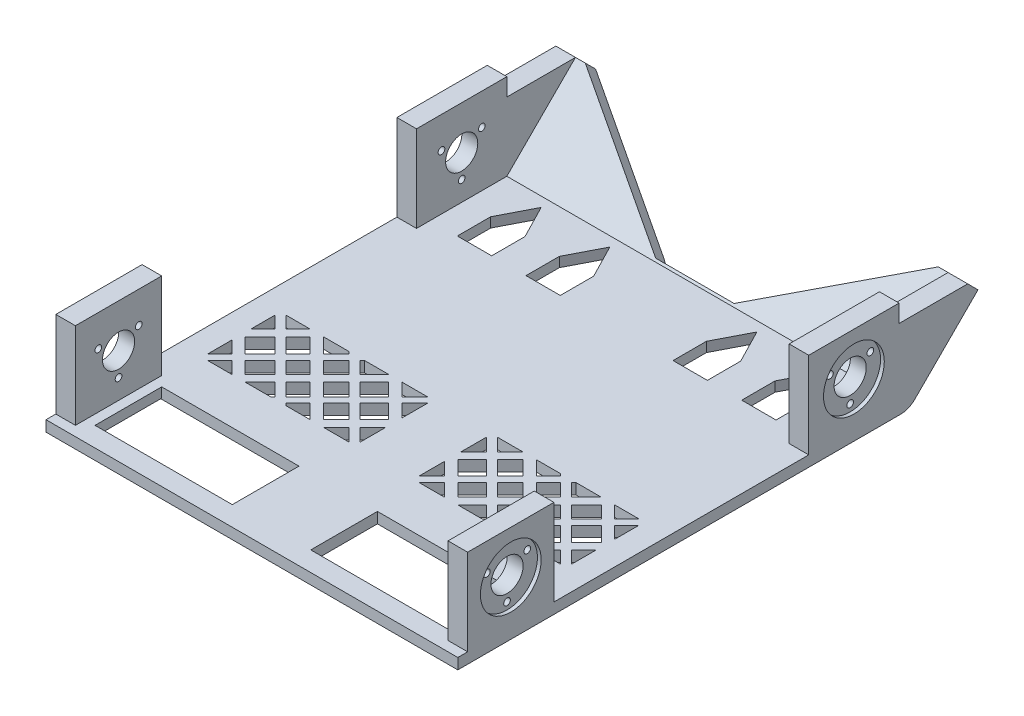
SolidWorks part; units mm, degrees
ref_plane "前视基准面" through (0, 0, 0) normal (0, 0, 1) x (1, 0, 0)
ref_plane "上视基准面" through (0, 0, 0) normal (0, 1, 0) x (1, 0, 0)
ref_plane "右视基准面" through (0, 0, 0) normal (1, 0, 0) x (0, 0, -1)
sketch "草图1" plane through (0, 0, 0) normal (0, 1, 0) x (1, 0, 0)
  line L0 (0, 0) -> (210, 0)
  line L1 (210, 0) -> (210, -230)
  line L2 (210, -230) -> (0, -230)
  line L3 (0, -230) -> (0, 0)
  line L4 (0, 0) -> (3, 0)
  line L5 (0, 0) -> (5, 0)
  line L6 (5, 0) -> (5, -230)
  line L7 (210, 0) -> (205, 0)
  line L8 (205, 0) -> (205, -230)
  line L9 (0, 0) -> (0, -10)
  line L10 (0, -10) -> (210, -10)
  line L11 (210, -230) -> (210, -220)
  line L12 (210, -220) -> (0, -220)
  line L13 (5, -10) -> (85, -10)
  line L14 (85, -10) -> (85, -44)
  line L15 (85, -44) -> (5, -44)
  line L16 (205, -10) -> (125, -10)
  line L17 (125, -10) -> (125, -44)
  line L18 (125, -44) -> (205, -44)
  line L19 (5, -220) -> (5, -186)
  line L20 (5, -186) -> (85, -186)
  line L21 (85, -186) -> (85, -220)
  line L22 (85, -220) -> (5, -220)
  line L23 (205, -220) -> (125, -220)
  line L24 (125, -220) -> (125, -186)
  line L25 (125, -186) -> (205, -186)
  line L26 (205, -186) -> (205, -220)
  line L27 (5, -10) -> (5, -44)
  line L28 (205, -44) -> (205, -10)
extrude "凸台-拉伸1" add sketch "草图1" along normal blind 5.5 contours L24 L25 L8 L18 L17 L10 L14 L15 L6 L20 L21 L12 | L3 L10 L6 L0 | L12 L6 L10 L3 | L6 L10 L8 L0 | L12 L1 L10 L8 | L8 L10 L1 L0 | L8 L12 L6 L2 | L6 L12 L3 L2 | L1 L12 L8 L2 region at (2.5, 0, 5) region at (2.5, 0, 115) region at (105, 0, 5) region at (2.5, 0, 225) region at (207.5, 0, 5) region at (105, 0, 225) region at (105, 0, 115) region at (207.5, 0, 115) region at (207.5, 0, 225)
sketch "草图3" plane through (0, 5.5, 0) normal (0, 1, 0) x (1, 0, 0)
  line L0 (85, -10) -> (85, 0)
  line L1 (0, 0) -> (210, 0) construction
  line L2 (85, 0) -> (85, -5)
  line L3 (85, -5) -> (0, -5)
  line L4 (0, -230) -> (0, 0) construction
  line L5 (0, -5) -> (0, -46.0662)
  line L6 (0, -46.0662) -> (0, -51.0662)
  line L7 (0, -51.0662) -> (5, -51.0662)
  line L8 (5, -51.0662) -> (5, -5)
  line L9 (105, 0) -> (105, -230)
  line L10 (210, -230) -> (0, -230) construction
  line L11 (5, -220) -> (5, -225)
  line L12 (5, -225) -> (0, -225)
  line L13 (0, -225) -> (0, -181)
  line L14 (0, -181) -> (5, -181)
  line L15 (5, -181) -> (5, -220)
  line L16 (210, -181) -> (205, -181)
  line L17 (210, -225) -> (210, -181)
  line L18 (205, -225) -> (210, -225)
  line L19 (205, -220) -> (205, -225)
  line L20 (205, -181) -> (205, -220)
  line L21 (5, -5) -> (5, -51.0662)
  line L22 (0, -51.0662) -> (0, -5)
  line L23 (210, -46.0662) -> (210, -51.0662)
  line L24 (210, -51.0662) -> (205, -51.0662)
  line L25 (205, -51.0662) -> (205, -5)
  line L26 (210, -5) -> (210, -46.0662)
  line L27 (205, -5) -> (210, -5)
extrude "凸台-拉伸2" add sketch "草图3" along normal blind 44 contours L7 L8 L17 L3 L10 | L15 L14 L10 L12 L11 L26 | L16 L20 L6 L19 L18 L2 | L27 L25 L22 L24 L2 region at (2.5, 5.5, 28.0331) region at (2.5, 5.5, 203) region at (207.5, 5.5, 203) region at (207.5, 5.5, 28.0331)
sketch "草图4" plane through (0, 0, 0) normal (-1, 0, 0) x (0, 0, 1)
  line L0 (5, 49.5) -> (51.0662, 5.5)
  line L1 (181, 49.5) -> (225, 5.5)
  circle A1 centre (203, 27.5) radius 17
  circle A2 centre (28.0331, 27.5) radius 15
  circle A3 centre (28.0331, 27.5) radius 8.2
  circle A4 centre (28.0331, 27.5) radius 11.9
  circle A5 centre (28.0331, 15.6) radius 1.7
  circle A6 centre (17.7274, 33.45) radius 1.7
  circle A7 centre (38.3388, 33.45) radius 1.7
  point P24 (28.0331, 27.5)
  dimension "D1" = 3
extrude "切除-拉伸1" cut sketch "草图4" against normal through all both and the other way through all contours A4 A6 | A4 A6 | A4 A7 | A4 A7 | A4 A5 | A4 A5 | L0 A3 | L0 A3 region at (0, 30.0167, 30.4369) region at (0, 24.9833, 25.6293) region at (0, 33.7996, 38.9443) region at (0, 33.0785, 37.6954) region at (0, 33.0785, 18.3708) region at (0, 33.7996, 17.1219) region at (0, 14.9008, 28.0331) region at (0, 16.3429, 28.0331)
sketch "草图5" plane through (0, 0, 0) normal (-1, 0, 0) x (0, 0, 1)
  circle A1 centre (28.0331, 27.5) radius 15.5
extrude "切除-拉伸3" cut sketch "草图5" against normal blind 1.9
sketch "草图6" plane through (210, 0, 0) normal (1, 0, 0) x (0, 0, -1)
  circle A0 centre (-28.0331, 27.5) radius 15.5
extrude "切除-拉伸4" cut sketch "草图6" against normal blind 1.9
sketch "草图7" plane through (0, 0, 0) normal (-1, 0, 0) x (0, 0, 1)
  line L0 (181, 49.5) -> (225, 5.5)
  line L1 (203, 27.5) -> (203, 15.6)
  circle A0 centre (203, 27.5) radius 11.9
  circle A1 centre (203, 27.5) radius 8.2
  circle A2 centre (203, 15.6) radius 1.7
  circle A3 centre (192.6943, 33.45) radius 1.7
  circle A4 centre (213.3057, 33.45) radius 1.7
  point P15 (203, 27.5)
  dimension "D1" = 3
extrude "切除-拉伸5" cut sketch "草图7" against normal through all both and the other way through all contours A0 A3 | A0 A3 | A0 A4 | A0 A4 | A0 A2 L1 | L1 A2 A0 | A0 A2 | L0 A1 | L0 A1 L1 | L1 A1 L0 region at (0, 29.9609, 205.4609) region at (0, 25.8594, 199.0393) region at (0, 33.7996, 213.9112) region at (0, 33.0785, 212.6623) region at (0, 33.0785, 193.3377) region at (0, 33.7996, 192.0888) region at (0, 22.5783, 205.0386) region at (0, 16.3429, 203.7042) region at (0, 16.3429, 202.2958) region at (0, 14.9008, 203)
sketch "草图8" plane through (0, 0, 0) normal (-1, 0, 0) x (0, 0, 1)
  circle A0 centre (203, 27.5) radius 15.5
extrude "切除-拉伸6" cut sketch "草图8" against normal blind 1.9
sketch "草图9" plane through (210, 0, 0) normal (1, 0, 0) x (0, 0, -1)
  circle A0 centre (-203, 27.5) radius 15.5
extrude "切除-拉伸7" cut sketch "草图9" against normal blind 1.9
sketch "草图10" plane through (0, 5.5, 0) normal (0, 1, 0) x (1, 0, 0)
  line L0 (5, -10) -> (15, -10)
  line L1 (5, -10) -> (85, -10) construction
  line L2 (15, -10) -> (15, -220)
  line L3 (85, -220) -> (5, -220) construction
  line L4 (15, -220) -> (5, -220)
  line L5 (5, -220) -> (5, -186)
  line L6 (5, -181) -> (5, -225) construction
  line L7 (5, -181) -> (5, -186) construction
  line L8 (5, -186) -> (15, -186)
  line L9 (5, -186) -> (85, -186) construction
  line L10 (5, -10) -> (5, -44)
  line L11 (5, -44) -> (15, -44)
  line L12 (85, -44) -> (5, -44) construction
  line L13 (205, -10) -> (195, -10)
  line L14 (125, -10) -> (205, -10) construction
  line L15 (195, -10) -> (195, -220)
  line L16 (205, -220) -> (125, -220) construction
  line L17 (195, -220) -> (205, -220)
  line L18 (205, -220) -> (205, -186)
  line L19 (205, -186) -> (195, -186)
  line L20 (125, -186) -> (205, -186) construction
  line L21 (205, -10) -> (205, -44)
  line L22 (205, -44) -> (195, -44)
  line L23 (125, -44) -> (205, -44) construction
  line M7 (5, -10) -> (85, -10)
  line M9 (85, -44) -> (5, -44)
  line M15 (5, -186) -> (85, -186)
  line M17 (85, -220) -> (5, -220)
  line M25 (205, -220) -> (125, -220)
  line M27 (125, -186) -> (205, -186)
  line M33 (205, -44) -> (125, -44)
  line M35 (125, -10) -> (205, -10)
extrude "凸台-拉伸3" add sketch "草图10" against normal blind 5 contours L21 L15 M35 M33 | L10 L2 M7 M9 | L5 L2 M17 M15 | L18 L15 M25 M27 region at (10, 5.5, 203) region at (10, 5.5, 27) region at (200, 5.5, 27) region at (200, 5.5, 203)
sketch "草图11" plane through (0, 5.5, 0) normal (0, 1, 0) x (1, 0, 0)
  line L0 (15, -10) -> (5, -10)
  line L1 (5, -51.0662) -> (5, -5) construction
  line L2 (10, -10) -> (10, -51.0662)
  line L3 (10, -51.0662) -> (5, -51.0662)
  line L4 (5, -51.0662) -> (5, -5)
  line L5 (5, -5) -> (10, -5)
  line L6 (10, -5) -> (10, -10)
  line L7 (10, -51.0662) -> (10, -230)
  line L8 (210, -230) -> (0, -230) construction
  line L9 (5, -225) -> (10, -225)
  line L10 (5, -181) -> (10, -181)
  line L11 (10, -181) -> (10, -225)
  line L12 (5, -181) -> (5, -225)
  line L13 (195, -10) -> (205, -10)
  line L14 (205, -51.0662) -> (205, -5) construction
  line L15 (200, -10) -> (200, -51.0662)
  line L16 (200, -51.0662) -> (205, -51.0662)
  line L17 (205, -51.0662) -> (205, -5)
  line L18 (205, -5) -> (200, -5)
  line L19 (200, -5) -> (200, -10)
  line L20 (200, -225) -> (205, -225)
  line L21 (205, -225) -> (205, -181)
  line L22 (205, -181) -> (200, -181)
  line L23 (200, -181) -> (200, -225)
  line M6 (5, -181) -> (5, -225)
  line M12 (205, -225) -> (205, -181)
  line M16 (205, -51.0662) -> (205, -5)
  line M22 (5, -5) -> (5, -51.0662)
extrude "凸台-拉伸4" add sketch "草图11" along normal blind 44 contours L3 L2 L0 M22 | L6 L5 L0 M22 | L18 L19 L13 M16 | L15 L16 L13 M16 | L10 L9 L7 M6 | L22 L23 L20 M12 region at (7.5, 5.5, 30.5331) region at (7.5, 5.5, 203) region at (7.5, 5.5, 7.5) region at (202.5, 5.5, 7.5) region at (202.5, 5.5, 30.5331) region at (202.5, 5.5, 203)
sketch "草图12" plane through (1.9, 0, 0) normal (-1, 0, 0) x (0, 0, 1)
  circle A0 centre (17.7274, 33.45) radius 1.7
  circle A1 centre (38.3388, 33.45) radius 1.7
  circle A2 centre (28.0331, 15.6) radius 1.7
  circle A3 centre (28.0331, 27.5) radius 8.2
  circle A4 centre (192.6943, 33.45) radius 1.7
  circle A5 centre (213.3057, 33.45) radius 1.7
  circle A6 centre (203, 15.6) radius 1.7
  circle A7 centre (203, 27.5) radius 8.2
extrude "切除-拉伸8" cut sketch "草图12" against normal through all both and the other way through all
sketch "草图13" plane through (210, 0, 0) normal (1, 0, 0) x (0, 0, -1)
  line L0 (-5, 5.5) -> (14.6466, 25.1466)
sketch "草图15" plane through (210, 0, 0) normal (1, 0, 0) x (0, 0, -1)
  line L0 (-5, 5.5) -> (-5, 40.5)
  line L1 (-5, 49.5) -> (-5, 5.5) construction
  line L2 (-5, 40.5) -> (31.0178, 40.5)
ref_plane "基准面5" through (0, 5.25, 5.25) normal (0, 0.7071, 0.7071) x (1, 0, 0)
sketch "草图17" plane through (0, 5.25, 5.25) normal (0, 0.7071, 0.7071) x (1, 0, 0)
  line L0 (210, 0.3536) -> (210, 49.8474)
  line L1 (210, 49.8474) -> (0, 49.8474)
  line L2 (0, 49.8474) -> (0, 0.3536)
  line L3 (0, 0.3536) -> (210, 0.3536)
extrude "凸台-拉伸5" add sketch "草图17" against normal through all
sketch "草图18" plane through (0, 0, 0) normal (-1, 0, 0) x (0, 0, 1)
  line L0 (-29.9975, 40.4975) -> (5, 40.5)
  line L1 (5, 40.5) -> (5, 5.5)
  line L2 (5, 5.5) -> (-29.9975, 40.4975)
extrude "凸台-拉伸6" add sketch "草图18" against normal blind 10
sketch "草图19" plane through (210, 0, 0) normal (1, 0, 0) x (0, 0, -1)
  line L0 (30, 40.5) -> (-5, 40.5)
  line L1 (-5, 40.5) -> (31.0178, 40.5) construction
  line L2 (40.3406, 50.8406) -> (-50.8406, -40.3406) construction
  line L3 (-5, 40.5) -> (-5, 5.5)
  line L4 (-5, 5.5) -> (30, 40.5)
extrude "凸台-拉伸8" add sketch "草图19" against normal blind 10
sketch "草图20" plane through (0, 5.25, 5.25) normal (0, 0.7071, 0.7071) x (1, 0, 0)
  line L0 (15, -3.182) -> (15, 49.8474)
  line L1 (200, 49.8474) -> (10, 49.8474) construction
  line L4 (125, 49.8474) -> (85, 49.8474)
  line L5 (85, 1.6082) -> (125, 1.6082)
  line L6 (125, 1.6082) -> (125, 49.8474)
  line L7 (85, 49.8474) -> (125, 49.8474)
  line L8 (85, 1.6082) -> (85, 49.8474)
  line L9 (15, 49.8474) -> (85, 1.6082)
  line L10 (195, -3.182) -> (195, 49.8474)
  line L11 (195, 49.8474) -> (125, 1.6082)
  line L12 (15, 1.6082) -> (85, 1.6082)
  line L13 (125, 1.6082) -> (195, 1.6082)
  line L14 (195, 1.6082) -> (195, 49.8474)
  line M4 (200, 49.8474) -> (10, 49.8474)
extrude "切除-拉伸9" cut sketch "草图20" against normal blind 10 contours L9 L8 M4 | L8 L5 L6 M4 | L11 L6 M4 region at (61.6667, 29.1274, -18.6274) region at (105, 23.4423, -12.9423) region at (148.3333, 29.1274, -18.6274)
sketch "草图21" plane through (0, 5.5, 0) normal (0, 1, 0) x (1, 0, 0)
  line L1 (15, -10) -> (85, -10) construction
  line L4 (125, -10) -> (195, -10) construction
  line L6 (32.5, -10) -> (15, -44)
  line L7 (32.5, -10) -> (50, -44)
  line L8 (85, -44) -> (15, -44) construction
  line L9 (50, -44) -> (67.5, -10)
  line L10 (67.5, -10) -> (85, -44)
  line L11 (125, -44) -> (142.5, -10)
  line L12 (142.5, -10) -> (160, -44)
  line L14 (160, -44) -> (177.5, -10)
  line L15 (177.5, -10) -> (195, -44)
  line L16 (15, -44) -> (15, -10)
  line L17 (15, -10) -> (32.5, -10)
  line L18 (32.5, -10) -> (67.5, -10)
  line L19 (67.5, -10) -> (85, -10)
  line L20 (85, -10) -> (85, -44)
  line L21 (125, -44) -> (125, -10)
  line L22 (125, -10) -> (142.5, -10)
  line L23 (142.5, -10) -> (177.5, -10)
  line L24 (177.5, -10) -> (195, -10)
  line L25 (195, -10) -> (195, -44)
  line L26 (41.25, -27) -> (41.25, -44)
  line L27 (58.75, -27) -> (58.75, -44)
  line L28 (151.25, -27) -> (151.25, -44)
  line L29 (125, -44) -> (195, -44) construction
  line L30 (168.75, -27) -> (168.75, -44)
  line L31 (41.25, -44) -> (58.75, -44)
  line L32 (151.25, -44) -> (168.75, -44)
  line M21 (15, -44) -> (15, -10)
  line M22 (15, -10) -> (85, -10)
  line M23 (85, -10) -> (85, -44)
  line M24 (85, -44) -> (15, -44)
  line M29 (125, -10) -> (195, -10)
  line M30 (195, -10) -> (195, -44)
  line M31 (195, -44) -> (125, -44)
  line M32 (125, -44) -> (125, -10)
extrude "凸台-拉伸11" add sketch "草图21" against normal blind 5 contours L6 M22 M21 | L7 L9 M22 | L7 L26 M24 | L27 L9 M24 | L10 M22 M23 | L11 M32 M29 | L12 L14 M29 | L15 M29 M30 | L30 L14 M31 | L12 L28 M31 region at (50, 5.5, 21.3333) region at (20.8333, 5.5, 21.3333) region at (44.1667, 5.5, 38.3333) region at (79.1667, 5.5, 21.3333) region at (55.8333, 5.5, 38.3333) region at (130.8333, 5.5, 21.3333) region at (160, 5.5, 21.3333) region at (154.1667, 5.5, 38.3333) region at (189.1667, 5.5, 21.3333) region at (165.8333, 5.5, 38.3333)
sketch "草图22" plane through (0, 0, 0) normal (-1, 0, 0) x (0, 0, 1)
  line L0 (0, 0.5) -> (0, 0)
  line L1 (0, 0) -> (-0.25, 0.25)
  line L2 (-0.25, 0.25) -> (0, 0.5)
extrude "凸台-拉伸13" add sketch "草图22" against normal blind 210
fillet "圆角1" radius 10 1 edges at (105, 0, 0)
sketch "草图23" plane through (0, 5.5, 0) normal (0, 1, 0) x (1, 0, 0)
  line L0 (23.75, -27) -> (23.75, -44)
  line L1 (32.5, -10) -> (15, -44) construction
  line L2 (41.25, -44) -> (15, -44) construction
  line L3 (23.75, -44) -> (15, -44)
  line L4 (15, -44) -> (23.75, -27)
  line L5 (76.25, -27) -> (76.25, -44)
  line L6 (67.5, -10) -> (85, -44) construction
  line L7 (85, -44) -> (58.75, -44) construction
  line L8 (76.25, -44) -> (85, -44)
  line L9 (85, -44) -> (76.25, -27)
  line L10 (133.75, -27) -> (133.75, -44)
  line L11 (125, -44) -> (142.5, -10) construction
  line L12 (125, -44) -> (151.25, -44) construction
  line L13 (133.75, -44) -> (125, -44)
  line L14 (125, -44) -> (133.75, -27)
  line L15 (186.25, -27) -> (186.25, -44)
  line L16 (177.5, -10) -> (195, -44) construction
  line L17 (168.75, -44) -> (195, -44) construction
  line L18 (186.25, -44) -> (195, -44)
  line L19 (195, -44) -> (186.25, -27)
extrude "凸台-拉伸14" add sketch "草图23" against normal blind 5 contours L4 L0 L3 | L9 L5 L8 | L14 L10 L13 | L19 L15 L18
sketch "草图24" plane through (0, 5.5, 0) normal (0, 1, 0) x (1, 0, 0)
  line L0 (0, -116.0331) -> (210, -116.0331) construction
  line L1 (0, -181) -> (0, -51.0662) construction
  line L2 (210, -51.0662) -> (210, -181) construction
  line L3 (105, -230) -> (105, -5) construction
  line L4 (210, -230) -> (0, -230) construction
  line L5 (10, -5) -> (200, -5) construction
  line L6 (197.8, -162.6296) -> (120, -162.6296)
  line L7 (12.2, -122.6296) -> (90, -122.6296)
  line L8 (12.2, -122.6296) -> (12.2, -162.6296)
  line L9 (12.2, -162.6296) -> (90, -162.6296)
  line L10 (90, -122.6296) -> (90, -162.6296)
  line L11 (120, -122.6296) -> (120, -162.6296)
  line L12 (197.8, -122.6296) -> (120, -122.6296)
  line L13 (197.8, -122.6296) -> (197.8, -162.6296)
  line L14 (12.2, -125.4296) -> (18.3835, -131.6131)
  line L15 (15, -122.6296) -> (21.1835, -128.8131)
  line L16 (90, -125.4296) -> (83.5137, -131.9159)
  line L17 (87.2, -122.6296) -> (80.7137, -129.1159)
  line L18 (12.2, -159.8296) -> (18.3835, -153.6461)
  line L19 (47.2, -122.6296) -> (48.3, -123.7296)
  line L20 (90, -159.8296) -> (83.5137, -153.3433)
  line L21 (15, -162.6296) -> (21.1835, -156.4461)
  line L22 (30.7972, -126.0598) -> (38.3835, -133.6461)
  line L23 (34.2274, -122.6296) -> (41.8137, -130.2159)
  line L24 (70.7972, -126.0598) -> (63.5137, -133.3433)
  line L25 (67.367, -122.6296) -> (60.0835, -129.9131)
  line L26 (74.2274, -162.6296) -> (80.7137, -156.1433)
  line L27 (70.7972, -159.1994) -> (77.2835, -152.7131)
  line L28 (27.367, -162.6296) -> (21.1835, -156.4461)
  line L29 (30.7972, -159.1994) -> (24.6137, -153.0159)
  line L30 (27.367, -122.6296) -> (21.1835, -128.8131)
  line L31 (30.7972, -126.0598) -> (24.6137, -132.2433)
  line L32 (74.2274, -122.6296) -> (80.7137, -129.1159)
  line L33 (70.7972, -126.0598) -> (77.2835, -132.5461)
  line L34 (18.3835, -131.6131) -> (12.2, -137.7966)
  line L35 (24.6137, -132.2433) -> (32.2, -139.8296)
  line L36 (21.8137, -135.0433) -> (29.4, -142.6296)
  line L37 (21.8137, -135.0433) -> (14.2274, -142.6296)
  line L38 (44.6137, -133.0159) -> (50.7972, -139.1994)
  line L39 (41.8137, -130.2159) -> (48.3, -123.7296)
  line L40 (41.1835, -136.4461) -> (47.367, -142.6296)
  line L41 (44.6137, -133.0159) -> (51.1, -126.5296)
  line L42 (32.2, -139.8296) -> (38.3835, -133.6461)
  line L43 (32.2, -145.4296) -> (38.3835, -151.6131)
  line L44 (35, -142.6296) -> (41.1835, -148.8131)
  line L45 (35, -142.6296) -> (41.1835, -136.4461)
  line L46 (21.8137, -150.2159) -> (29.4, -142.6296)
  line L47 (18.3835, -153.6461) -> (12.2, -147.4626)
  line L48 (21.8137, -150.2159) -> (14.2274, -142.6296)
  line L49 (24.6137, -153.0159) -> (32.2, -145.4296)
  line L50 (41.8137, -155.0433) -> (48.3, -161.5296)
  line L51 (44.6137, -152.2433) -> (51.1, -158.7296)
  line L52 (50.7972, -146.0598) -> (57.2835, -152.5461)
  line L53 (54.2274, -142.6296) -> (60.7137, -149.1159)
  line L54 (60.7137, -136.1433) -> (67.2, -142.6296)
  line L55 (60.0835, -129.9131) -> (53.9, -123.7296)
  line L56 (77.2835, -132.5461) -> (70, -139.8296)
  line L57 (80.0835, -135.3461) -> (72.8, -142.6296)
  line L58 (80.0835, -149.9131) -> (72.8, -142.6296)
  line L59 (80.7137, -156.1433) -> (87.2, -162.6296)
  line L60 (60.0835, -155.3461) -> (53.9, -161.5296)
  line L61 (57.2835, -152.5461) -> (51.1, -158.7296)
  line L62 (50.7972, -146.0598) -> (44.6137, -152.2433)
  line L63 (47.367, -142.6296) -> (41.1835, -148.8131)
  line L64 (51.1, -126.5296) -> (57.2835, -132.7131)
  line L65 (53.9, -123.7296) -> (55, -122.6296)
  line L66 (57.2835, -132.7131) -> (50.7972, -139.1994)
  line L67 (60.7137, -136.1433) -> (54.2274, -142.6296)
  line L68 (67.2, -142.6296) -> (60.7137, -149.1159)
  line L69 (70, -145.4296) -> (63.5137, -151.9159)
  line L70 (80.0835, -149.9131) -> (87.367, -142.6296)
  line L71 (83.5137, -153.3433) -> (90, -146.857)
  line L72 (38.3835, -151.6131) -> (30.7972, -159.1994)
  line L73 (41.8137, -155.0433) -> (34.2274, -162.6296)
  line L74 (48.3, -161.5296) -> (47.2, -162.6296)
  line L75 (53.9, -161.5296) -> (55, -162.6296)
  line L76 (60.0835, -155.3461) -> (67.367, -162.6296)
  line L77 (63.5137, -151.9159) -> (70.7972, -159.1994)
  line L78 (70, -145.4296) -> (77.2835, -152.7131)
  line L79 (70, -139.8296) -> (63.5137, -133.3433)
  line L80 (80.0835, -135.3461) -> (87.367, -142.6296)
  line L81 (83.5137, -131.9159) -> (90, -138.4021)
  line L82 (126.4863, -131.9159) -> (120, -138.4021)
  line L83 (129.9165, -135.3461) -> (122.633, -142.6296)
  line L84 (140, -139.8296) -> (146.4863, -133.3433)
  line L85 (140, -145.4296) -> (132.7165, -152.7131)
  line L86 (146.4863, -151.9159) -> (139.2028, -159.1994)
  line L87 (149.9165, -155.3461) -> (142.633, -162.6296)
  line L88 (156.1, -161.5296) -> (155, -162.6296)
  line L89 (161.7, -161.5296) -> (162.8, -162.6296)
  line L90 (168.1863, -155.0433) -> (175.7726, -162.6296)
  line L91 (171.6165, -151.6131) -> (179.2028, -159.1994)
  line L92 (126.4863, -153.3433) -> (120, -146.857)
  line L93 (129.9165, -149.9131) -> (122.633, -142.6296)
  line L94 (140, -145.4296) -> (146.4863, -151.9159)
  line L95 (142.8, -142.6296) -> (149.2863, -149.1159)
  line L96 (149.2863, -136.1433) -> (155.7726, -142.6296)
  line L97 (152.7165, -132.7131) -> (159.2028, -139.1994)
  line L98 (156.1, -123.7296) -> (155, -122.6296)
  line L99 (158.9, -126.5296) -> (152.7165, -132.7131)
  line L100 (162.633, -142.6296) -> (168.8165, -148.8131)
  line L101 (159.2028, -146.0598) -> (165.3863, -152.2433)
  line L102 (152.7165, -152.5461) -> (158.9, -158.7296)
  line L103 (149.9165, -155.3461) -> (156.1, -161.5296)
  line L104 (129.2863, -156.1433) -> (122.8, -162.6296)
  line L105 (129.9165, -149.9131) -> (137.2, -142.6296)
  line L106 (129.9165, -135.3461) -> (137.2, -142.6296)
  line L107 (132.7165, -132.5461) -> (140, -139.8296)
  line L108 (149.9165, -129.9131) -> (156.1, -123.7296)
  line L109 (149.2863, -136.1433) -> (142.8, -142.6296)
  line L110 (155.7726, -142.6296) -> (149.2863, -149.1159)
  line L111 (159.2028, -146.0598) -> (152.7165, -152.5461)
  line L112 (165.3863, -152.2433) -> (158.9, -158.7296)
  line L113 (168.1863, -155.0433) -> (161.7, -161.5296)
  line L114 (185.3863, -153.0159) -> (177.8, -145.4296)
  line L115 (188.1863, -150.2159) -> (195.7726, -142.6296)
  line L116 (191.6165, -153.6461) -> (197.8, -147.4626)
  line L117 (188.1863, -150.2159) -> (180.6, -142.6296)
  line L118 (175, -142.6296) -> (168.8165, -136.4461)
  line L119 (175, -142.6296) -> (168.8165, -148.8131)
  line L120 (177.8, -145.4296) -> (171.6165, -151.6131)
  line L121 (177.8, -139.8296) -> (171.6165, -133.6461)
  line L122 (165.3863, -133.0159) -> (158.9, -126.5296)
  line L123 (168.8165, -136.4461) -> (162.633, -142.6296)
  line L124 (168.1863, -130.2159) -> (161.7, -123.7296)
  line L125 (165.3863, -133.0159) -> (159.2028, -139.1994)
  line L126 (188.1863, -135.0433) -> (195.7726, -142.6296)
  line L127 (188.1863, -135.0433) -> (180.6, -142.6296)
  line L128 (185.3863, -132.2433) -> (177.8, -139.8296)
  line L129 (191.6165, -131.6131) -> (197.8, -137.7966)
  line L130 (139.2028, -126.0598) -> (132.7165, -132.5461)
  line L131 (135.7726, -122.6296) -> (129.2863, -129.1159)
  line L132 (179.2028, -126.0598) -> (185.3863, -132.2433)
  line L133 (182.633, -122.6296) -> (188.8165, -128.8131)
  line L134 (179.2028, -159.1994) -> (185.3863, -153.0159)
  line L135 (182.633, -162.6296) -> (188.8165, -156.4461)
  line L136 (139.2028, -159.1994) -> (132.7165, -152.7131)
  line L137 (135.7726, -162.6296) -> (129.2863, -156.1433)
  line L138 (142.633, -122.6296) -> (149.9165, -129.9131)
  line L139 (139.2028, -126.0598) -> (146.4863, -133.3433)
  line L140 (175.7726, -122.6296) -> (168.1863, -130.2159)
  line L141 (179.2028, -126.0598) -> (171.6165, -133.6461)
  line L142 (195, -162.6296) -> (188.8165, -156.4461)
  line L143 (120, -159.8296) -> (126.4863, -153.3433)
  line L144 (162.8, -122.6296) -> (161.7, -123.7296)
  line L145 (197.8, -159.8296) -> (191.6165, -153.6461)
  line L146 (122.8, -122.6296) -> (129.2863, -129.1159)
  line L147 (120, -125.4296) -> (126.4863, -131.9159)
  line L148 (195, -122.6296) -> (188.8165, -128.8131)
  line L149 (197.8, -125.4296) -> (191.6165, -131.6131)
  line L150 (120, -122.6296) -> (120, -162.6296)
  line L151 (197.8, -162.6296) -> (120, -162.6296)
  line L152 (197.8, -122.6296) -> (197.8, -162.6296)
  line L153 (197.8, -122.6296) -> (120, -122.6296)
  dimension "D1" = 2.8
  dimension "D2" = 2.8
  dimension "D3" = 45
  dimension "D4" = 2.8
  dimension "D5" = 40
  dimension "D6" = 77.8
  dimension "D7" = 2.8
  dimension "D8" = 45
  dimension "D9" = 6.5965
  dimension "D10" = 15
  dimension "D11" = 45
  dimension "D12" = 45
  dimension "D13" = 2.8
  dimension "D14" = 2.8
  dimension "D15" = 2.8
  dimension "D16" = 2.8
extrude "切除-拉伸10" cut sketch "草图24" against normal blind 5.5 contours L71 L20 L10 | L80 L57 L58 L70 | L59 L26 L9 | L78 L69 L77 L27 | L7 L32 L17 | L16 L81 L10 | L79 L56 L33 L24 | L68 L54 L67 L53 | L65 L55 L25 L7 | L66 L64 L41 L38 | L76 L60 L75 L9 | L52 L62 L51 L61 | L63 L40 L45 L44 | L23 L39 L19 L7 | L74 L50 L73 L9 | L72 L43 L49 L29 | L35 L42 L22 L31 | L48 L46 L36 L37 | L30 L7 L15 | L34 L14 L8 | L18 L47 L8 | L9 L28 L21 | L110 L96 L109 L95 | L112 L101 L111 L102 | L118 L123 L100 L119 | L125 L122 L99 L97 | L132 L141 L121 L128 | L12 L144 L124 L140 | L148 L12 L133 | L13 L149 L129 | L126 L127 L117 L115 | L145 L13 L116 | L6 L142 L135 | L91 L134 L114 L120 | L90 L113 L89 L6 | L103 L87 L6 L88 | L136 L86 L94 L85 | L6 L137 L104 | L11 L143 L92 | L139 L130 L107 L84 | L12 L138 L108 L98 | L106 L83 L93 L105 | L12 L146 L131 | L147 L11 L82 region at (188.8165, 5.5, 160.5684) region at (195.7388, 5.5, 153.6461) region at (168.3256, 5.5, 160.0544) region at (195.7388, 5.5, 131.6131) region at (149.7722, 5.5, 160.1536) region at (188.8165, 5.5, 124.6908) region at (129.2863, 5.5, 160.4675) region at (168.3256, 5.5, 125.2048) region at (122.1621, 5.5, 153.3433) region at (149.7722, 5.5, 125.1055) region at (122.1621, 5.5, 131.9159) region at (129.2863, 5.5, 124.7917) region at (21.1835, 5.5, 124.6908) region at (14.2612, 5.5, 131.6131) region at (41.6744, 5.5, 125.2048) region at (14.2612, 5.5, 153.6461) region at (60.2278, 5.5, 125.1055) region at (21.1835, 5.5, 160.5684) region at (80.7137, 5.5, 124.7917) region at (41.6744, 5.5, 160.0544) region at (87.8379, 5.5, 131.9159) region at (60.2278, 5.5, 160.1536) region at (87.8379, 5.5, 153.3433) region at (80.7137, 5.5, 160.4675) region at (31.4986, 5.5, 132.9447) region at (70.3986, 5.5, 132.9447) region at (70.3986, 5.5, 152.3145) region at (31.4986, 5.5, 152.3145) region at (21.8137, 5.5, 142.6296) region at (50.9486, 5.5, 132.8645) region at (41.1835, 5.5, 142.6296) region at (50.9486, 5.5, 152.3947) region at (60.7137, 5.5, 142.6296) region at (80.0835, 5.5, 142.6296) region at (129.9165, 5.5, 142.6296) region at (139.6014, 5.5, 132.9447) region at (139.6014, 5.5, 152.3145) region at (178.5014, 5.5, 152.3145) region at (149.2863, 5.5, 142.6296) region at (159.0514, 5.5, 132.8645) region at (168.8165, 5.5, 142.6296) region at (159.0514, 5.5, 152.3947) region at (188.1863, 5.5, 142.6296) region at (178.5014, 5.5, 132.9447)
